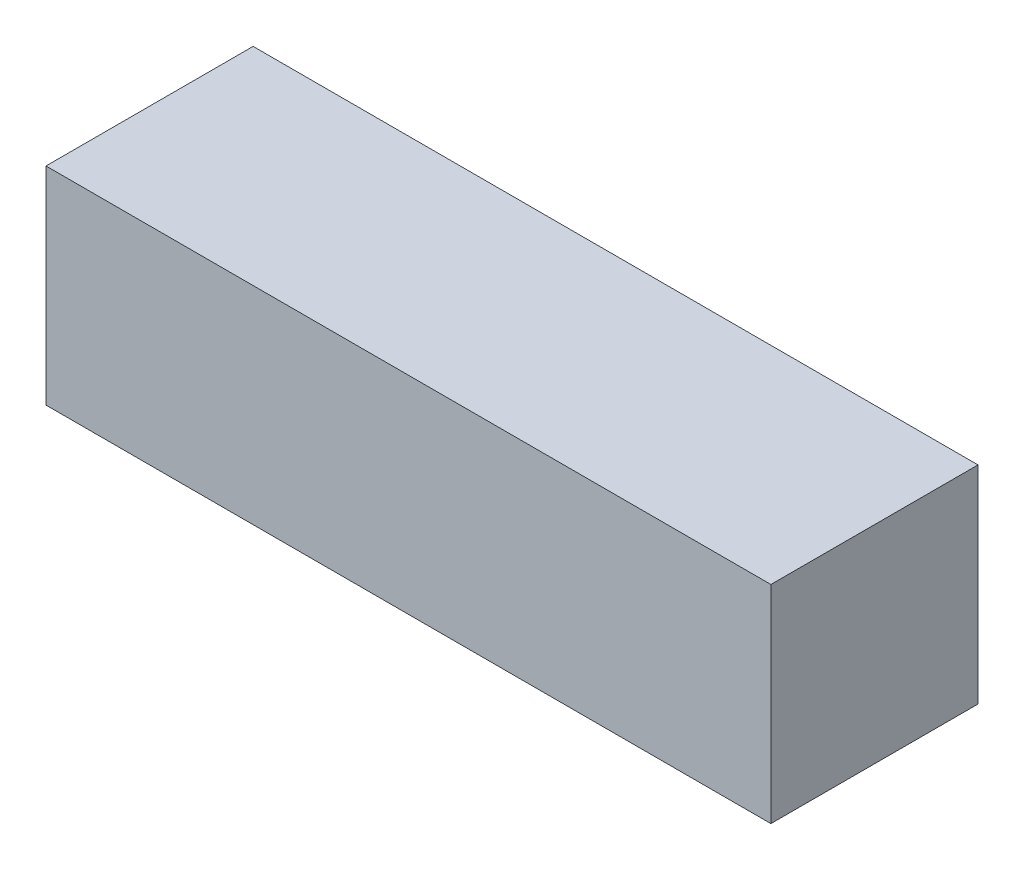
SolidWorks part; units mm, degrees
ref_plane "Płaszczyzna przednia" through (0, 0, 0) normal (0, 0, 1) x (1, 0, 0)
ref_plane "Płaszczyzna górna" through (0, 0, 0) normal (0, 1, 0) x (1, 0, 0)
ref_plane "Płaszczyzna prawa" through (0, 0, 0) normal (1, 0, 0) x (0, 0, -1)
sketch "Szkic1" plane through (0, 0, 0) normal (0, 0, 1) x (1, 0, 0)
  line L1 (-35, -10) -> (35, -10)
  line L2 (-35, -10) -> (-35, 10)
  line L3 (-35, 10) -> (35, 10)
  line L4 (35, -10) -> (35, 10)
  line L5 (-35, -10) -> (35, 10) construction
  line L6 (-35, 10) -> (35, -10) construction
  point P0 (0, 0)
  dimension "D1" = 70
  dimension "D2" = 20
extrude "Dodanie-wyciągnięcie1" add sketch "Szkic1" along normal blind 10 and the other way blind 10
